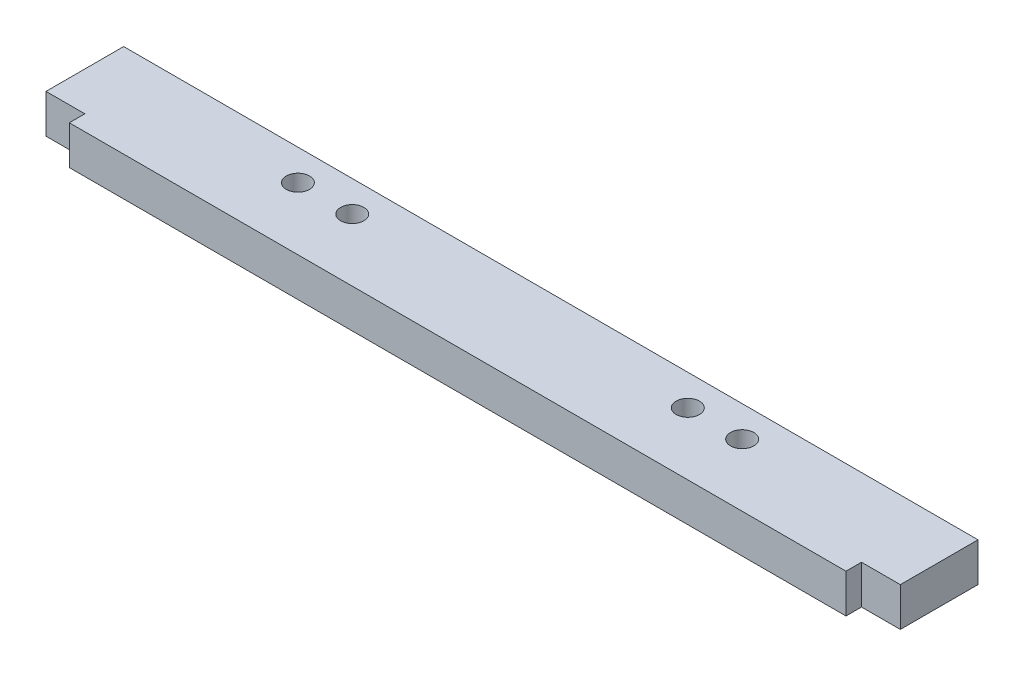
SolidWorks part; units mm, degrees
ref_plane "Front Plane" through (0, 0, 0) normal (0, 0, 1) x (1, 0, 0)
ref_plane "Top Plane" through (0, 0, 0) normal (0, 1, 0) x (1, 0, 0)
ref_plane "Right Plane" through (0, 0, 0) normal (1, 0, 0) x (0, 0, -1)
sketch "Sketch1" plane through (0, 0, 0) normal (1, 0, 0) x (0, 0, -1)
  line L1 (-2.1369, 5.602) -> (9.8631, 5.602)
  line L2 (-2.1369, 5.602) -> (-2.1369, 0.602)
  line L3 (-2.1369, 0.602) -> (9.8631, 0.602)
  line L4 (9.8631, 5.602) -> (9.8631, 0.602)
  dimension "D1" = 12
  dimension "D2" = 5
extrude "Boss-Extrude1" add sketch "Sketch1" along normal blind 110
sketch "Sketch2" plane through (0, 0.602, 0) normal (0, -1, 0) x (1, 0, 0)
  line L1 (0, -9.8631) -> (5, -9.8631)
  line L2 (0, -9.8631) -> (0, -7.3631)
  line L3 (0, -7.3631) -> (5, -7.3631)
  line L4 (5, -9.8631) -> (5, -7.3631)
  dimension "D1" = 5
  dimension "D2" = 2.5
sketch "Sketch5" plane through (0, 0, 0) normal (-1, 0, 0) x (0, 0, 1)
  line L0 (0, 0.602) -> (0, 5.602) construction
  line L1 (2.1369, 0.602) -> (-9.8631, 0.602) construction
  line L2 (-9.8631, 5.602) -> (2.1369, 5.602) construction
sketch "Sketch6" plane through (0, 5.602, 0) normal (0, 1, 0) x (1, 0, 0)
  line L1 (0, -2.1369) -> (5, -2.1369)
  line L2 (0, -2.1369) -> (0, -0.1369)
  line L3 (0, -0.1369) -> (5, -0.1369)
  line L4 (5, -2.1369) -> (5, -0.1369)
  dimension "D1" = 5
  dimension "D2" = 2
sketch "Sketch7" plane through (0, 5.602, 0) normal (0, 1, 0) x (1, 0, 0)
  line L0 (110, 3.8631) -> (0, 0) construction
  line L1 (110, 9.8631) -> (110, -2.1369) construction
  line L2 (55, 1.9316) -> (55, -2.1369) construction
  line L3 (110, -2.1369) -> (0, -2.1369) construction
sketch "Sketch8" plane through (0, 0, 2.1369) normal (0, 0, 1) x (1, 0, 0)
  line L0 (55, 5.602) -> (55, 0.602) construction
  line L1 (110, 0.602) -> (0, 0.602) construction
ref_plane "Plane3" through (55, 0, 0) normal (1, 0, 0) x (0, 0, -1)
sketch "Sketch13" plane through (0, 5.602, 0) normal (0, 1, 0) x (1, 0, 0)
  line L0 (55, 1.9316) -> (4.7941, 1.9316) construction
  line L1 (29.897, 1.9316) -> (29.897, 9.8631) construction
  line L2 (110, 9.8631) -> (0, 9.8631) construction
  line L3 (29.897, 5.8973) -> (26.397, 5.8973) construction
  line L4 (17.3455, 5.8973) -> (17.3455, 9.8631) construction
  line L5 (29.897, 5.8973) -> (33.397, 5.8973) construction
  dimension "D1" = 3.5
  dimension "D2" = 3.5
hole_wizard "M3 Tapped Hole1" positions "3DSketch2" profile "Sketch14" tap size "M3" standard "ISO"
sketch3d "3DSketch2"
  point P0 (26.397, 5.602, -5.8973)
  point P3 (33.397, 5.602, -5.8973)
sketch "Sketch14" plane through (26.397, 5.602, -5.8973) normal (1, 0, 0) x (0, 0, 1)
  line L0 (0, 0) -> (0, 8.2511)
  line L1 (0, 8.2511) -> (1.25, 7.5)
  line L2 (1.25, 7.5) -> (1.25, 6)
  line L3 (1.25, 6) -> (1.5, 6)
  line L4 (1.5, 6) -> (1.5, 0)
  line L5 (1.5, 0) -> (0, 0)
  line L10 (0, 8.2511) -> (-1.25, 7.5) construction
  line L11 (0, -6.35) -> (0, 107.95) construction
  dimension "Tap Drill Dia." = 2.5
  dimension "Tap Drill Depth" = 7.5
  dimension "Thread Major Dia." = 3
  dimension "Thread Depth" = 6
  dimension "Drill Angle" = 118
ref_plane "Plane4" through (55, 0, 0) normal (1, 0, 0) x (0, 0, -1)
mirror "Mirror3" about plane through (55, 0, 0) normal (1, 0, 0) of "M3 Tapped Hole1"
extrude "Cut-Extrude1" cut sketch "Sketch6" against normal blind 10 contours L4 L3 L2 L1
mirror "Mirror4" about plane through (55, 0, 0) normal (1, 0, 0) of "Cut-Extrude1"
